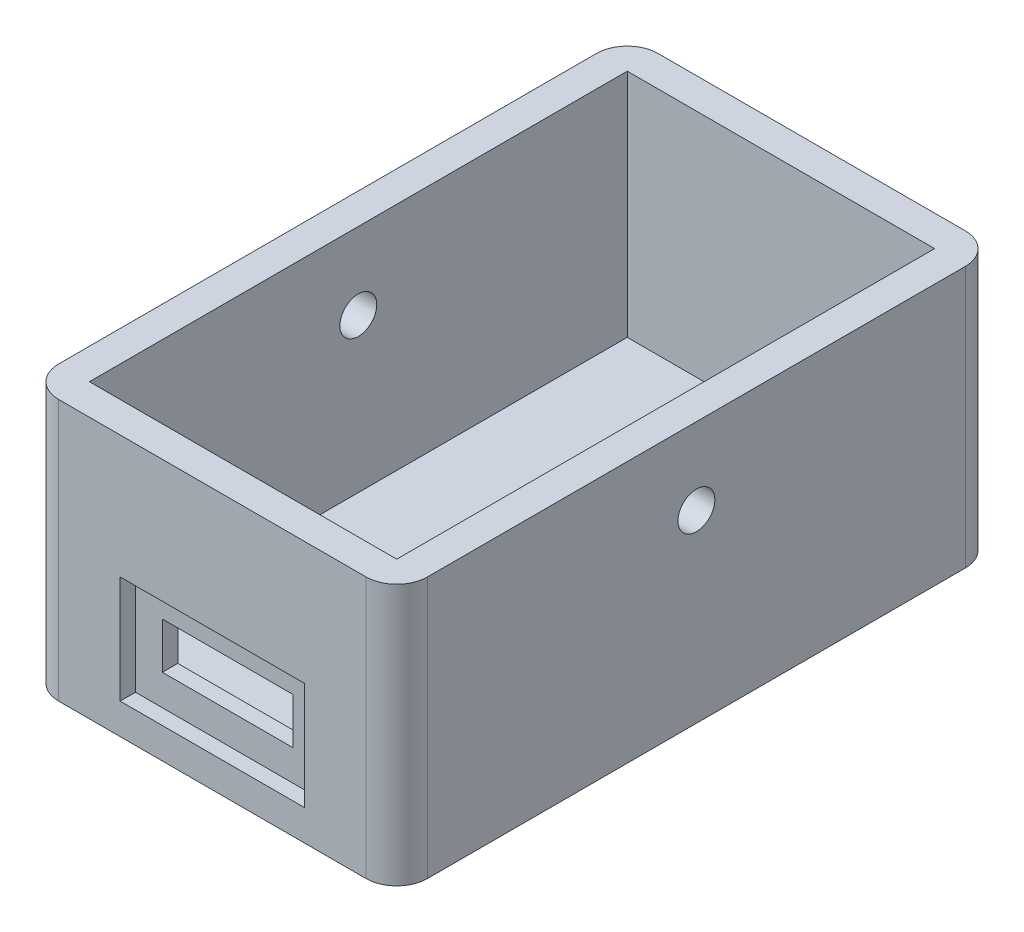
SolidWorks part; units mm, degrees
ref_plane "Ön Düzlem" through (0, 0, 0) normal (0, 0, 1) x (1, 0, 0)
ref_plane "Üst Düzlem" through (0, 0, 0) normal (0, 1, 0) x (1, 0, 0)
ref_plane "Sağ Düzlem" through (0, 0, 0) normal (1, 0, 0) x (0, 0, -1)
sketch "Çizim1" plane through (0, 0, 0) normal (0, 1, 0) x (1, 0, 0)
  line L1 (-14.4706, 14.1176) -> (9.5294, 14.1176)
  line L2 (-14.4706, 14.1176) -> (-14.4706, -24.8824)
  line L3 (-14.4706, -24.8824) -> (9.5294, -24.8824)
  line L4 (9.5294, 14.1176) -> (9.5294, -24.8824)
  dimension "D1" = 24
  dimension "D2" = 39
extrude "Yükseklik-Ekstrüzyon1" add sketch "Çizim1" along normal blind 17
fillet "Radyus1" radius 2 4 edges at (-14.4706, 8.5, -14.1176) (-14.4706, 8.5, 24.8824) (9.5294, 8.5, 24.8824) (9.5294, 8.5, -14.1176)
shell "İç Boşaltma1" thickness 2 removed face at (-2.4706, 17, 5.3824)
sketch "Çizim2" plane through (0, 0, 24.8824) normal (0, 0, 1) x (1, 0, 0)
  line L1 (-6.7206, 7) -> (1.7794, 7)
  line L2 (-6.7206, 7) -> (-6.7206, 4)
  line L3 (-6.7206, 4) -> (1.7794, 4)
  line L4 (1.7794, 7) -> (1.7794, 4)
  line L6 (7.5294, 0) -> (7.5294, 17) construction
  line L7 (-12.4706, 0) -> (7.5294, 0) construction
  dimension "D1" = 8.5
  dimension "D2" = 3
  dimension "D3" = 5.75
  dimension "D4" = 4
extrude "Kes-Ekstrüzyon1" cut sketch "Çizim2" against normal blind 17
sketch "Çizim3" plane through (0, 0, 24.8824) normal (0, 0, 1) x (1, 0, 0)
  line L0 (-6.7206, 4) -> (1.7794, 4) construction
  line L1 (-8.4706, 9) -> (3.5294, 9)
  line L2 (-8.4706, 9) -> (-8.4706, 2)
  line L3 (-8.4706, 2) -> (3.5294, 2)
  line L4 (3.5294, 9) -> (3.5294, 2)
  line L5 (-6.7206, 7) -> (-6.7206, 4) construction
  dimension "D1" = 12
  dimension "D2" = 7
  dimension "D3" = 2
  dimension "D4" = 1.75
extrude "Kes-Ekstrüzyon2" cut sketch "Çizim3" against normal blind 1
ref_plane "Düzlem3" through (9.6938, 0, 0) normal (1, 0, 0) x (0, 0, -1)
sketch "Çizim5" plane through (9.5294, 0, 0) normal (1, 0, 0) x (0, 0, -1)
  line L0 (-22.8824, 17) -> (12.1176, 17) construction
  line L1 (-22.8824, 17) -> (-22.8824, 0) construction
  circle A0 centre (-5.3824, 12) radius 1.2
  dimension "D1" = 5
  dimension "D2" = 17.5
extrude "Kes-Ekstrüzyon3" cut sketch "Çizim5" against normal blind 30
